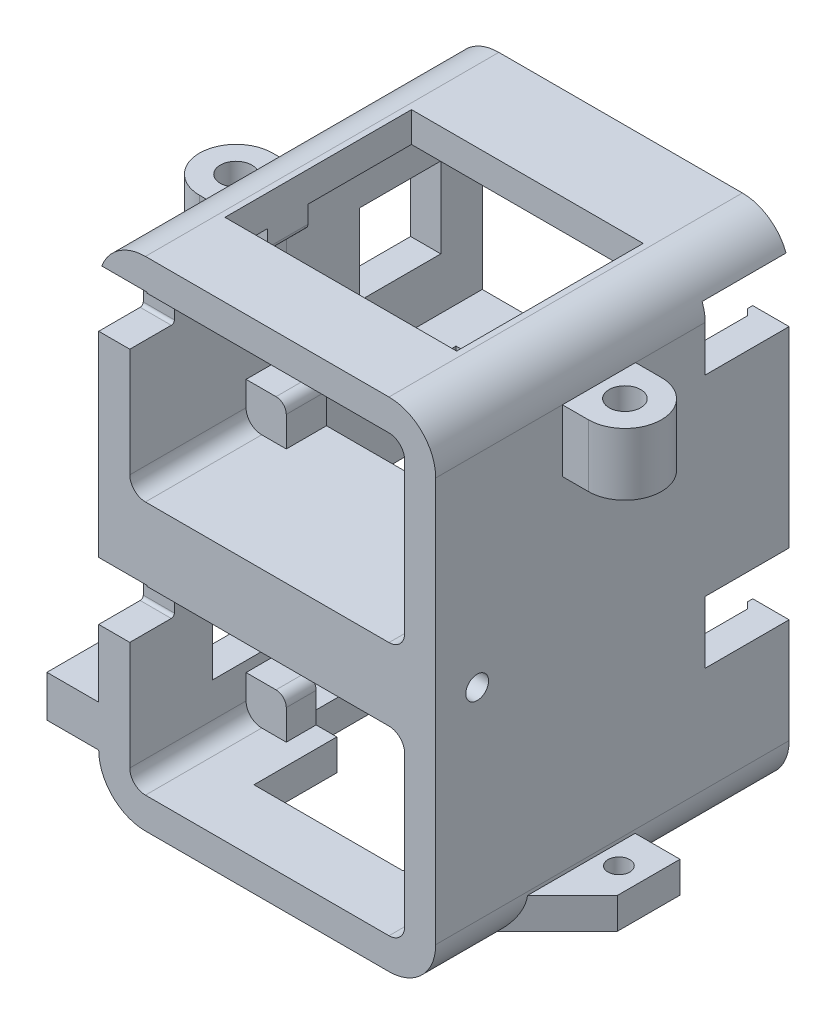
SolidWorks part; units mm, degrees
ref_plane "前视基准面" through (0, 0, 0) normal (0, 0, 1) x (1, 0, 0)
ref_plane "上视基准面" through (0, 0, 0) normal (0, 1, 0) x (1, 0, 0)
ref_plane "右视基准面" through (0, 0, 0) normal (1, 0, 0) x (0, 0, -1)
other "Configuration Table"
sketch "草图2" plane through (0, 0, 0) normal (0, 0, 1) x (1, 0, 0)
  line L20 (13.26, -7.25) -> (13.26, 7.25)
  line L21 (11.75, 8.76) -> (-16.76, 8.76)
  line L22 (-16.76, 8.76) -> (-16.76, 3.34)
  line L23 (-16.76, 3.34) -> (-13.26, 3.34)
  line L24 (-13.26, 3.34) -> (-13.26, -7.25)
  line L25 (-11.75, -8.76) -> (-3.99, -8.76)
  line L26 (-3.99, -8.76) -> (-3.99, -7.76)
  line L27 (-3.99, -7.76) -> (3.99, -7.76)
  line L28 (3.99, -7.76) -> (3.99, -8.76)
  line L29 (3.99, -8.76) -> (11.75, -8.76)
  line L40 (13.26, -7.25) -> (13.26, 7.25)
  line L41 (11.75, 8.76) -> (-16.76, 8.76)
  line L42 (-16.76, 8.76) -> (-16.76, 3.34)
  line L43 (-16.76, 3.34) -> (-13.26, 3.34)
  line L44 (-13.26, 3.34) -> (-13.26, -7.25)
  line L45 (-11.75, -8.76) -> (-3.99, -8.76)
  line L49 (3.99, -8.76) -> (11.75, -8.76)
  line L50 (-3.99, 15.74) -> (3.99, 15.74)
  line L51 (-3.99, -8.76) -> (3.99, -8.76)
  line L52 (-3.99, 12.74) -> (3.99, 12.74)
  line L53 (3.99, 12.74) -> (11.75, 12.74)
  line L54 (16.26, 17.25) -> (16.26, 31.75)
  line L55 (11.75, 36.26) -> (-19.76, 36.26)
  line L56 (-19.76, 36.26) -> (-19.76, 24.84)
  line L57 (-19.76, 24.84) -> (-16.26, 24.84)
  line L58 (-16.26, 24.84) -> (-16.26, 17.25)
  line L59 (-11.75, 12.74) -> (-3.99, 12.74)
  line L70 (13.26, 17.25) -> (13.26, 31.75)
  line L71 (11.75, 33.26) -> (-16.76, 33.26)
  line L72 (-16.76, 33.26) -> (-16.76, 27.84)
  line L73 (-16.76, 27.84) -> (-13.26, 27.84)
  line L74 (-13.26, 27.84) -> (-13.26, 17.25)
  line L75 (-11.75, 15.74) -> (-3.99, 15.74)
  line L76 (-3.99, 15.74) -> (-3.99, 16.74)
  line L77 (-3.99, 16.74) -> (3.99, 16.74)
  line L78 (3.99, 16.74) -> (3.99, 15.74)
  line L79 (3.99, 15.74) -> (11.75, 15.74)
  line L80 (13.26, 17.25) -> (13.26, 31.75)
  line L81 (11.75, 33.26) -> (-16.76, 33.26)
  line L82 (-16.76, 33.26) -> (-16.76, 27.84)
  line L83 (-16.76, 27.84) -> (-13.26, 27.84)
  line L84 (-13.26, 27.84) -> (-13.26, 17.25)
  line L85 (-11.75, 15.74) -> (-3.99, 15.74)
  line L89 (3.99, 15.74) -> (11.75, 15.74)
  line L90 (16.26, -7.25) -> (16.26, 7.25)
  line L91 (11.75, 11.76) -> (-19.76, 11.76)
  line L92 (-19.76, 11.76) -> (-19.76, 0.34)
  line L93 (-19.76, 0.34) -> (-16.26, 0.34)
  line L94 (-16.26, 0.34) -> (-16.26, -7.25)
  line L95 (-11.75, -11.76) -> (-3.99, -11.76)
  line L96 (-3.99, -11.76) -> (3.99, -11.76)
  line L97 (3.99, -11.76) -> (11.75, -11.76)
  line L98 (-16.26, 0.34) -> (-16.26, 3.34)
  line L99 (-16.26, 17.25) -> (-16.26, 11.76)
  line L100 (16.26, 17.25) -> (16.26, 7.25)
  line L101 (-16.76, 33.26) -> (-19.76, 33.26)
  line L102 (-16.76, 27.84) -> (-19.76, 27.84)
  line L103 (-16.76, 8.76) -> (-19.76, 8.76)
  line L104 (-16.26, 24.84) -> (-16.26, 27.84)
  line L105 (-16.26, 36.26) -> (-16.26, 33.26)
  line L106 (-16.26, 11.76) -> (-16.26, 8.76)
  line L107 (-16.26, 33.26) -> (-16.26, 27.84)
  line L108 (-16.26, 8.76) -> (-16.26, 3.34)
  line L109 (-13.26, 27.84) -> (-13.26, 33.26)
  line L110 (-13.26, 3.34) -> (-13.26, 8.76)
  arc A1 (-11.75, 11.76) -> (-16.26, 7.25) centre (-11.75, 7.25) ccw
  arc A2 (-11.75, 8.76) -> (-13.26, 7.25) centre (-11.75, 7.25) ccw
  arc A3 (-11.75, 8.76) -> (-13.26, 7.25) centre (-11.75, 7.25) ccw
  arc A6 (13.26, 7.25) -> (11.75, 8.76) centre (11.75, 7.25) ccw
  arc A7 (-13.26, -7.25) -> (-11.75, -8.76) centre (-11.75, -7.25) ccw
  arc A8 (11.75, -8.76) -> (13.26, -7.25) centre (11.75, -7.25) ccw
  arc A12 (13.26, 7.25) -> (11.75, 8.76) centre (11.75, 7.25) ccw
  arc A13 (-13.26, -7.25) -> (-11.75, -8.76) centre (-11.75, -7.25) ccw
  arc A14 (11.75, -8.76) -> (13.26, -7.25) centre (11.75, -7.25) ccw
  arc A15 (11.75, 12.74) -> (16.26, 17.25) centre (11.75, 17.25) ccw
  arc A16 (16.26, 31.75) -> (11.75, 36.26) centre (11.75, 31.75) ccw
  arc A17 (-16.26, 17.25) -> (-11.75, 12.74) centre (-11.75, 17.25) ccw
  arc A21 (13.26, 31.75) -> (11.75, 33.26) centre (11.75, 31.75) ccw
  arc A22 (-13.26, 17.25) -> (-11.75, 15.74) centre (-11.75, 17.25) ccw
  arc A23 (11.75, 15.74) -> (13.26, 17.25) centre (11.75, 17.25) ccw
  arc A24 (13.26, 31.75) -> (11.75, 33.26) centre (11.75, 31.75) ccw
  arc A25 (-13.26, 17.25) -> (-11.75, 15.74) centre (-11.75, 17.25) ccw
  arc A26 (11.75, 15.74) -> (13.26, 17.25) centre (11.75, 17.25) ccw
  arc A27 (16.26, 7.25) -> (11.75, 11.76) centre (11.75, 7.25) ccw
  arc A28 (-16.26, -7.25) -> (-11.75, -11.76) centre (-11.75, -7.25) ccw
  arc A29 (11.75, -11.76) -> (16.26, -7.25) centre (11.75, -7.25) ccw
  arc A31 (-11.75, 36.26) -> (-16.26, 31.75) centre (-11.75, 31.75) ccw
  arc A32 (-11.75, 33.26) -> (-13.26, 31.75) centre (-11.75, 31.75) ccw
  arc A33 (-11.75, 33.26) -> (-13.26, 31.75) centre (-11.75, 31.75) ccw
  dimension "D4" = 3
  dimension "D6" = 3
  dimension "D7" = 0.01
  dimension "D8" = 3
extrude "凸台-拉伸2" add sketch "草图2" against normal up to surface (11.22 mm away)
sketch "草图3" plane through (0, 0, -11.22) normal (0, 0, -1) x (-1, 0, 0)
  line L0 (11.75, -8.76) -> (-11.75, -8.76) construction
  line L2 (-11.75, 8.76) -> (11.75, 8.76) construction
  line L3 (11.75, -8.76) -> (-11.75, -8.76)
  line L4 (16.26, -7.25) -> (16.26, 31.75)
  line L5 (11.75, 36.26) -> (-11.75, 36.26)
  line L6 (-16.26, 31.75) -> (-16.26, -7.25)
  line L7 (-11.75, -11.76) -> (11.75, -11.76)
  line L12 (16.26, -7.25) -> (16.26, 31.75)
  line L13 (11.75, 36.26) -> (-11.75, 36.26)
  line L14 (-16.26, 31.75) -> (-16.26, -7.25)
  line L16 (-11.75, -11.76) -> (11.75, -11.76)
  line L20 (-13.26, -7.25) -> (-13.26, 7.25)
  line L21 (-11.75, 33.26) -> (11.75, 33.26) construction
  line L22 (-13.26, 17.25) -> (-13.26, 31.75) construction
  line L23 (-9.38, -8.74) -> (-9.38, -5.87)
  line L24 (-10.37, -4.88) -> (-13.24, -4.88)
  line L25 (-13.24, -4.88) -> (-13.24, -7.25)
  line L26 (-11.75, -8.74) -> (-9.38, -8.74)
  line L27 (-9.38, -8.74) -> (-9.38, -5.87)
  line L28 (-10.37, -4.88) -> (-13.24, -4.88)
  line L32 (11.75, 15.74) -> (-11.75, 15.74) construction
  line L33 (-11.75, 33.26) -> (11.75, 33.26)
  line L34 (-13.26, 17.25) -> (-13.26, 31.75)
  line L36 (11.75, 15.74) -> (-11.75, 15.74)
  line L38 (13.26, 7.25) -> (13.26, -7.25) construction
  line L39 (13.24, -4.88) -> (10.37, -4.88)
  line L40 (9.38, -5.87) -> (9.38, -8.74)
  line L41 (9.38, -8.74) -> (11.75, -8.74)
  line L42 (13.24, -7.25) -> (13.24, -4.88)
  line L43 (13.24, -4.88) -> (10.37, -4.88)
  line L44 (9.38, -5.87) -> (9.38, -8.74)
  line L47 (13.26, 7.25) -> (13.26, -7.25)
  line L48 (-11.75, 8.76) -> (11.75, 8.76) construction
  line L49 (-9.38, 15.75) -> (-9.38, 18.63)
  line L50 (-10.37, 19.62) -> (-13.25, 19.62)
  line L51 (-13.24, 6.68) -> (-11.67, 6.68)
  line L52 (-11.18, 7.17) -> (-11.18, 8.74)
  line L53 (-11.18, 8.74) -> (-11.75, 8.74)
  line L54 (-13.24, 7.25) -> (-13.24, 6.68)
  line L55 (-13.24, 6.68) -> (-11.67, 6.68)
  line L56 (-11.18, 7.17) -> (-11.18, 8.74)
  line L59 (-13.24, 6.68) -> (-13.26, 6.68)
  line L60 (-13.26, -7.25) -> (-13.26, 7.25) construction
  line L61 (-9.38, 15.74) -> (-9.38, 18.63)
  line L62 (-10.37, 19.62) -> (-13.26, 19.62)
  line L63 (11.18, 8.74) -> (11.18, 7.17)
  line L64 (11.67, 6.68) -> (13.24, 6.68)
  line L65 (13.24, 6.68) -> (13.24, 7.25)
  line L66 (11.75, 8.74) -> (11.18, 8.74)
  line L67 (11.18, 8.76) -> (11.18, 7.17)
  line L68 (11.67, 6.68) -> (13.26, 6.68)
  line L71 (-11.75, 8.76) -> (11.75, 8.76)
  line L73 (-13.25, 31.18) -> (-11.67, 31.18)
  line L74 (-11.18, 31.67) -> (-11.18, 33.25)
  line L75 (-13.25, 31.18) -> (-11.67, 31.18)
  line L76 (-11.18, 31.67) -> (-11.18, 33.25)
  line L79 (11.67, 31.18) -> (13.25, 31.18)
  line L80 (11.18, 33.25) -> (11.18, 31.67)
  line L81 (11.67, 31.18) -> (13.26, 31.18)
  line L82 (11.18, 33.25) -> (11.18, 31.67)
  line L83 (-13.25, 31.18) -> (-13.26, 31.18)
  line L84 (-11.18, 33.25) -> (-11.18, 33.26)
  line L85 (9.38, 18.63) -> (9.38, 15.75)
  line L86 (13.25, 19.62) -> (10.37, 19.62)
  line L87 (9.38, 18.63) -> (9.38, 15.74)
  line L88 (13.26, 19.62) -> (10.37, 19.62)
  line L89 (11.18, 33.25) -> (11.18, 33.26)
  line L90 (-11.18, 8.74) -> (-11.18, 8.76)
  line L91 (13.26, 31.75) -> (13.26, 17.25) construction
  line L92 (13.26, 31.75) -> (13.26, 17.25)
  line L93 (-13.24, -4.88) -> (-13.26, -4.88)
  line L94 (-9.38, -8.74) -> (-9.38, -8.76)
  line L95 (9.38, -8.74) -> (9.38, -8.76)
  line L96 (13.24, -4.88) -> (13.26, -4.88)
  arc A0 (-13.26, -7.25) -> (-11.75, -8.76) centre (-11.75, -7.25) ccw construction
  arc A1 (11.75, -8.76) -> (13.26, -7.25) centre (11.75, -7.25) ccw construction
  arc A2 (-11.75, 8.76) -> (-13.26, 7.25) centre (-11.75, 7.25) ccw construction
  arc A3 (11.75, -11.76) -> (16.26, -7.25) centre (11.75, -7.25) ccw
  arc A4 (-11.75, 36.26) -> (-16.26, 31.75) centre (-11.75, 31.75) ccw
  arc A5 (-16.26, -7.25) -> (-11.75, -11.76) centre (-11.75, -7.25) ccw
  arc A6 (11.75, -11.76) -> (16.26, -7.25) centre (11.75, -7.25) ccw
  arc A9 (-11.75, 36.26) -> (-16.26, 31.75) centre (-11.75, 31.75) ccw
  arc A10 (-9.38, -5.87) -> (-10.37, -4.88) centre (-10.37, -5.87) ccw
  arc A11 (-13.24, -7.25) -> (-11.75, -8.74) centre (-11.75, -7.25) ccw
  arc A12 (-9.38, -5.87) -> (-10.37, -4.88) centre (-10.37, -5.87) ccw
  arc A14 (-16.26, -7.25) -> (-11.75, -11.76) centre (-11.75, -7.25) ccw
  arc A15 (-13.26, -7.25) -> (-11.75, -8.76) centre (-11.75, -7.25) ccw
  arc A16 (11.75, -8.76) -> (13.26, -7.25) centre (11.75, -7.25) ccw
  arc A17 (-11.75, 8.76) -> (-13.26, 7.25) centre (-11.75, 7.25) ccw
  arc A18 (10.37, -4.88) -> (9.38, -5.87) centre (10.37, -5.87) ccw
  arc A19 (11.75, -8.74) -> (13.24, -7.25) centre (11.75, -7.25) ccw
  arc A20 (10.37, -4.88) -> (9.38, -5.87) centre (10.37, -5.87) ccw
  arc A22 (-11.75, 33.26) -> (-13.26, 31.75) centre (-11.75, 31.75) ccw construction
  arc A23 (11.75, 15.74) -> (13.26, 17.25) centre (11.75, 17.25) ccw construction
  arc A24 (-11.67, 6.68) -> (-11.18, 7.17) centre (-11.67, 7.17) ccw
  arc A25 (-11.75, 8.74) -> (-13.24, 7.25) centre (-11.75, 7.25) ccw
  arc A26 (-11.67, 6.68) -> (-11.18, 7.17) centre (-11.67, 7.17) ccw
  arc A28 (-13.26, 17.25) -> (-11.75, 15.74) centre (-11.75, 17.25) ccw construction
  arc A29 (-11.75, 33.26) -> (-13.26, 31.75) centre (-11.75, 31.75) ccw
  arc A30 (11.18, 7.17) -> (11.67, 6.68) centre (11.67, 7.17) ccw
  arc A31 (13.24, 7.25) -> (11.75, 8.74) centre (11.75, 7.25) ccw
  arc A32 (11.18, 7.17) -> (11.67, 6.68) centre (11.67, 7.17) ccw
  arc A34 (11.75, 15.74) -> (13.26, 17.25) centre (11.75, 17.25) ccw
  arc A35 (-13.26, 17.25) -> (-11.75, 15.74) centre (-11.75, 17.25) ccw
  arc A36 (13.26, 7.25) -> (11.75, 8.76) centre (11.75, 7.25) ccw construction
  arc A37 (13.26, 7.25) -> (11.75, 8.76) centre (11.75, 7.25) ccw
  arc A38 (-9.38, 18.63) -> (-10.37, 19.62) centre (-10.37, 18.63) ccw
  arc A39 (-9.38, 18.63) -> (-10.37, 19.62) centre (-10.37, 18.63) ccw
  arc A41 (-11.67, 31.18) -> (-11.18, 31.67) centre (-11.67, 31.67) ccw
  arc A42 (-11.67, 31.18) -> (-11.18, 31.67) centre (-11.67, 31.67) ccw
  arc A44 (11.18, 31.67) -> (11.67, 31.18) centre (11.67, 31.67) ccw
  arc A45 (11.18, 31.67) -> (11.67, 31.18) centre (11.67, 31.67) ccw
  arc A46 (13.26, 31.75) -> (11.75, 33.26) centre (11.75, 31.75) ccw construction
  arc A47 (10.37, 19.62) -> (9.38, 18.63) centre (10.37, 18.63) ccw
  arc A48 (10.37, 19.62) -> (9.38, 18.63) centre (10.37, 18.63) ccw
  arc A49 (13.26, 31.75) -> (11.75, 33.26) centre (11.75, 31.75) ccw
  arc A52 (16.26, 31.75) -> (11.75, 36.26) centre (11.75, 31.75) ccw
  arc A53 (16.26, 31.75) -> (11.75, 36.26) centre (11.75, 31.75) ccw
  dimension "D7" = 0.01
  dimension "D9" = 0.01
extrude "凸台-拉伸3" add sketch "草图3" along normal up to surface (3.88 mm away)
sketch "草图4" plane through (-16.26, 0, 0) normal (-1, 0, 0) x (0, 0, 1)
  line L8 (0.1, 8.85) -> (-4, 8.85)
  line L9 (-4.3, 8.55) -> (-4.3, 3.55)
  line L10 (-4, 3.25) -> (0.1, 3.25)
  line L11 (0.1, 3.25) -> (0.1, 8.85)
  line L12 (0.1, 8.85) -> (-4, 8.85)
  line L13 (-4.3, 8.55) -> (-4.3, 3.55)
  line L14 (-4, 3.25) -> (0.1, 3.25)
  line L15 (0.1, 3.25) -> (0.1, 8.85)
  line L20 (0.1, 33.35) -> (-4, 33.35)
  line L21 (-4.3, 33.05) -> (-4.3, 28.05)
  line L22 (-4, 27.75) -> (0.1, 27.75)
  line L23 (0.1, 27.75) -> (0.1, 33.35)
  line L24 (0.1, 33.35) -> (-4, 33.35)
  line L25 (-4.3, 33.05) -> (-4.3, 28.05)
  line L26 (-4, 27.75) -> (0.1, 27.75)
  line L27 (0.1, 27.75) -> (0.1, 33.35)
  arc A4 (-4, 8.85) -> (-4.3, 8.55) centre (-4, 8.55) ccw
  arc A5 (-4.3, 3.55) -> (-4, 3.25) centre (-4, 3.55) ccw
  arc A6 (-4, 8.85) -> (-4.3, 8.55) centre (-4, 8.55) ccw
  arc A7 (-4.3, 3.55) -> (-4, 3.25) centre (-4, 3.55) ccw
  arc A10 (-4, 33.35) -> (-4.3, 33.05) centre (-4, 33.05) ccw
  arc A11 (-4.3, 28.05) -> (-4, 27.75) centre (-4, 28.05) ccw
  arc A12 (-4, 33.35) -> (-4.3, 33.05) centre (-4, 33.05) ccw
  arc A13 (-4.3, 28.05) -> (-4, 27.75) centre (-4, 28.05) ccw
extrude "切除-拉伸1" cut sketch "草图4" against normal blind 4.65
ref_plane "基准面1" through (0, 31.75, 0) normal (0, 1, 0) x (1, 0, 0)
sketch "草图8" plane through (0, 31.75, 0) normal (0, 1, 0) x (1, 0, 0)
  line L0 (18.76, 12.23) -> (15.235, 12.23)
  line L1 (15.235, 12.23) -> (15.235, 15.755)
  line L2 (16.26, 15.1) -> (16.26, 0) construction
  line L3 (-12.113, 15.755) -> (15.235, 15.755) construction
  line L4 (9.73, 15.91) -> (-9.73, 15.91) construction
  line L5 (-9.73, 15.6) -> (9.73, 15.6) construction
  line L9 (18.76, 19.28) -> (15.235, 19.28)
  line L10 (15.235, 15.755) -> (15.235, 19.28)
  circle A2 centre (18.76, 15.755) radius 1.525
  circle A3 centre (18.76, 15.755) radius 3.525
  dimension "D1" = 3.05
  dimension "D3" = 2.5
  dimension "D2" = 2
extrude "凸台-拉伸5" add sketch "草图8" against normal blind 6 contours A3 A2 | A3 L9 L10 | A3 L1 L0
mirror "镜向1" about plane through (0, 0, 0) normal (1, 0, 0) of "凸台-拉伸5"
sketch "草图9" plane through (0, 0, -15.1) normal (0, 0, -1) x (-1, 0, 0)
  line L0 (-11.18, 33.26) -> (11.18, 33.26) construction
  line L1 (-11.18, 33.26) -> (11.18, 33.26)
  line L2 (-11.18, 33.26) -> (-11.18, 36.26)
  line L3 (-11.18, 36.26) -> (11.18, 36.26)
  line L4 (11.18, 33.26) -> (11.18, 36.26)
  line L5 (11.75, 36.26) -> (-11.75, 36.26) construction
  line L6 (-11.18, 31.67) -> (-11.18, 33.26) construction
  line L7 (11.18, 33.26) -> (11.18, 31.67) construction
extrude "切除-拉伸3" cut sketch "草图9" against normal blind 8
sketch "草图10" plane through (0, 0, -15.1) normal (0, 0, -1) x (-1, 0, 0)
  line L0 (-11.75, -11.76) -> (11.75, -11.76) construction
  line L1 (-10.73, -11.76) -> (10.73, -11.76)
  line L2 (-10.73, -11.76) -> (-10.73, -4.88)
  line L3 (-10.73, -4.88) -> (10.73, -4.88)
  line L4 (10.73, -11.76) -> (10.73, -4.88)
  line L5 (13.26, -4.88) -> (10.37, -4.88) construction
  line L6 (-9.73, 21.7989) -> (-9.73, 20.8989) construction
  line L7 (9.73, 69.5489) -> (9.73, -48.1511) construction
  dimension "D1" = 1
  dimension "D2" = 1
extrude "切除-拉伸4" cut sketch "草图10" against normal blind 1
sketch "草图12" plane through (-16.26, 0, 0) normal (-1, 0, 0) x (0, 0, 1)
  line L0 (0, 8.85) -> (0, 27.75) construction
  line L1 (-11.22, 8.76) -> (-4.2142, 8.76) construction
  line L2 (-11.22, 15.74) -> (0, 15.74) construction
  line L3 (-11.22, 8.76) -> (-4.2142, 8.76)
  line L4 (-11.22, 15.74) -> (0, 15.74)
  line L5 (-8.8508, 12.25) -> (0.722, 12.25) construction
  circle A0 centre (-4, 12.25) radius 1.1
  dimension "D1" = 2.2
  dimension "D2" = 4
extrude "切除-拉伸5" cut sketch "草图12" against normal blind 8 contours A0 L5 | L5 A0
mirror "镜向2" about plane through (0, 0, 0) normal (1, 0, 0) of "切除-拉伸5"
sketch "草图14" plane through (0, 0, -15.1) normal (0, 0, -1) x (-1, 0, 0)
  line L0 (-16.26, 19.53) -> (16.26, 19.53)
  line L2 (-16.26, 8.85) -> (16.26, 8.85)
  line L3 (-10.37, 19.63) -> (-13.25, 19.63) construction
  line L6 (9.88, -48.3011) -> (9.88, 69.6193)
  line L7 (-9.88, -48.3011) -> (9.88, -48.3011)
  line L8 (-9.88, 69.6193) -> (-9.88, -48.3011)
  line L9 (9.88, -48.3011) -> (9.88, 69.6193)
  line L10 (-9.88, -48.3011) -> (9.88, -48.3011)
  line L11 (-9.88, 69.6193) -> (-9.88, -48.3011)
  line L13 (-11.17, 8.75) -> (11.17, 8.75) construction
  line L19 (16.26, 3.25) -> (13.26, 3.25)
  line L20 (16.26, -7.25) -> (16.26, 3.25)
  line L21 (-11.75, -11.76) -> (11.75, -11.76)
  line L22 (-16.26, 31.75) -> (-16.26, -7.25)
  line L23 (11.75, 36.26) -> (-11.75, 36.26)
  line L24 (11.61, 33.35) -> (15.9666, 33.35)
  line L26 (-11.75, 33.26) -> (11.61, 33.26)
  line L27 (-13.26, 17.25) -> (-13.26, 31.75)
  line L28 (11.75, 15.74) -> (-11.75, 15.74)
  line L29 (13.26, 27.75) -> (13.26, 17.25)
  line L30 (16.26, 27.75) -> (13.26, 27.75)
  line L31 (16.26, 8.85) -> (16.26, 27.75)
  line L32 (11.61, 8.85) -> (16.26, 8.85)
  line L34 (-11.75, 8.76) -> (11.61, 8.76)
  line L35 (-13.26, -7.25) -> (-13.26, 7.25)
  line L36 (11.75, -8.76) -> (-11.75, -8.76)
  line L37 (13.26, 3.25) -> (13.26, -7.25)
  line L39 (16.26, -7.25) -> (16.26, 8.85)
  line L40 (-11.75, -11.76) -> (11.75, -11.76)
  line L41 (-16.26, 31.75) -> (-16.26, -7.25)
  line L42 (11.75, 36.26) -> (-11.75, 36.26)
  line L50 (16.26, 8.85) -> (16.26, 31.75)
  line L66 (11.61, 33.26) -> (11.61, 33.35)
  line L67 (11.61, 8.76) -> (11.61, 8.85)
  arc A2 (9.88, 69.6193) -> (-9.88, 69.6193) centre (0, 57.7742) ccw
  arc A3 (9.88, 69.6193) -> (-9.88, 69.6193) centre (0, 57.7742) ccw
  arc A10 (11.75, -11.76) -> (16.26, -7.25) centre (11.75, -7.25) ccw
  arc A11 (-16.26, -7.25) -> (-11.75, -11.76) centre (-11.75, -7.25) ccw
  arc A12 (-11.75, 36.26) -> (-16.26, 31.75) centre (-11.75, 31.75) ccw
  arc A13 (15.9666, 33.35) -> (11.75, 36.26) centre (11.75, 31.75) ccw
  arc A14 (-11.75, 33.26) -> (-13.26, 31.75) centre (-11.75, 31.75) ccw
  arc A15 (-13.26, 17.25) -> (-11.75, 15.74) centre (-11.75, 17.25) ccw
  arc A16 (11.75, 15.74) -> (13.26, 17.25) centre (11.75, 17.25) ccw
  arc A17 (-11.75, 8.76) -> (-13.26, 7.25) centre (-11.75, 7.25) ccw
  arc A18 (-13.26, -7.25) -> (-11.75, -8.76) centre (-11.75, -7.25) ccw
  arc A19 (11.75, -8.76) -> (13.26, -7.25) centre (11.75, -7.25) ccw
  arc A20 (11.75, -11.76) -> (16.26, -7.25) centre (11.75, -7.25) ccw
  arc A21 (-16.26, -7.25) -> (-11.75, -11.76) centre (-11.75, -7.25) ccw
  arc A22 (-11.75, 36.26) -> (-16.26, 31.75) centre (-11.75, 31.75) ccw
  arc A23 (16.26, 31.75) -> (11.75, 36.26) centre (11.75, 31.75) ccw
  dimension "D3" = 0.1
  dimension "D4" = 0.1
  dimension "D2" = 0.15
extrude "凸台-拉伸7" add sketch "草图14" along normal blind 3
sketch "草图15" plane through (0, 0, -15.1) normal (0, 0, -1) x (-1, 0, 0)
  line L0 (-16.26, 25.75) -> (-16.26, 19.53) construction
  line L7 (-16.26, 19.53) -> (-16.26, 8.85) construction
  line L8 (-16.26, 8.85) -> (-16.26, -7.25) construction
  line L10 (-10.73, -11.76) -> (10.73, -11.76) construction
  line L22 (16.26, -7.25) -> (16.26, 8.85) construction
  line L23 (16.26, 8.85) -> (16.26, 19.53) construction
  line L32 (16.26, 19.53) -> (16.26, 25.75) construction
  line L37 (11.18, 36.26) -> (-11.18, 36.26) construction
  line L38 (-16.26, 31.75) -> (-16.26, 19.53)
  line L39 (-16.26, 19.53) -> (-16.26, 8.85)
  line L42 (-16.26, 8.85) -> (-16.26, -7.25)
  line L43 (-11.75, -11.76) -> (11.75, -11.76)
  line L44 (16.26, -7.25) -> (16.26, 8.85)
  line L45 (16.26, 8.85) -> (16.26, 19.53)
  line L46 (16.26, 19.53) -> (16.26, 31.75)
  line L47 (11.75, 36.26) -> (-11.75, 36.26)
  line L48 (-11.17, 33.25) -> (11.17, 33.25) construction
  line L49 (-13.35, 33.35) -> (13.35, 33.35)
  line L54 (-13.35, 33.35) -> (-13.35, -8.85)
  line L55 (-13.35, -8.85) -> (13.35, -8.85)
  line L56 (13.35, 33.35) -> (13.35, -8.85)
  line L58 (13.25, 6.67) -> (13.25, -4.87) construction
  line L59 (9.37, -8.75) -> (-9.37, -8.75) construction
  line L60 (-13.25, -4.87) -> (-13.25, 6.67) construction
  arc A8 (-16.26, -7.25) -> (-11.75, -11.76) centre (-11.75, -7.25) ccw construction
  arc A9 (11.75, -11.76) -> (16.26, -7.25) centre (11.75, -7.25) ccw construction
  arc A10 (16.26, 31.75) -> (11.75, 36.26) centre (11.75, 31.75) ccw construction
  arc A11 (-11.75, 36.26) -> (-16.26, 31.75) centre (-11.75, 31.75) ccw construction
  arc A12 (-16.26, -7.25) -> (-11.75, -11.76) centre (-11.75, -7.25) ccw
  arc A13 (11.75, -11.76) -> (16.26, -7.25) centre (11.75, -7.25) ccw
  arc A14 (16.26, 31.75) -> (11.75, 36.26) centre (11.75, 31.75) ccw
  arc A15 (-11.75, 36.26) -> (-16.26, 31.75) centre (-11.75, 31.75) ccw
  dimension "D2" = 0.1
  dimension "D1" = 0.1
  dimension "D3" = 0.1
  dimension "D4" = 0.1
extrude "凸台-上半部分" add sketch "草图15" along normal blind 19
sketch "草图16" plane through (0, 0, -18.1) normal (0, 0, -1) x (-1, 0, 0)
  line L1 (-13.35, 8.85) -> (13.35, 8.85)
  line L2 (-13.35, 8.85) -> (-13.35, 15.65)
  line L3 (-13.35, 15.65) -> (13.35, 15.65)
  line L4 (13.35, 8.85) -> (13.35, 15.65)
  line L12 (-13.35, 33.35) -> (-13.35, -8.85) construction
  line L13 (13.35, 33.35) -> (13.35, -8.85) construction
  line L15 (-4, 15.75) -> (-11.75, 15.75) construction
  line L16 (-11.17, 8.75) -> (11.17, 8.75) construction
  dimension "D2" = 0.1
  dimension "D1" = 0.1
extrude "凸台-拉伸9" add sketch "草图16" along normal up to surface (16 mm away) up to face at (0, 12.25, -34.1)
sketch "草图11" plane through (0, -13.58, 0) normal (0, 1, 0) x (1, 0, 0)
  line L2 (11.75, 34.1) -> (11.75, 0)
  line L3 (11.75, 34.1) -> (11.75, 0) construction
  line L7 (15.88, 21.655) -> (15.88, 16.405)
  line L8 (15.88, 16.405) -> (17.4201, 16.405)
  line L9 (17.4201, 15.105) -> (15.88, 15.105)
  line L10 (15.88, 15.105) -> (15.88, 9.855)
  line L11 (15.88, 9.855) -> (20.58, 9.855)
  line L12 (20.58, 9.855) -> (20.58, 21.655)
  line L13 (20.58, 21.655) -> (15.88, 21.655)
  line L19 (20.58, 13.9124) -> (20.58, 18.755)
  line L21 (11.75, 18.755) -> (20.58, 18.755)
  line L22 (20.58, 13.9124) -> (11.75, 5.0824)
  circle A0 centre (18.18, 15.755) radius 1.1
  arc A1 (17.4201, 15.105) -> (17.4201, 16.405) centre (18.18, 15.755) ccw
  line M15 (15.88, 21.655) -> (15.88, 16.405)
  line M16 (15.88, 16.405) -> (17.4201, 16.405)
  line M18 (17.4201, 15.105) -> (15.88, 15.105)
  line M19 (15.88, 15.105) -> (15.88, 9.855)
  line M20 (15.88, 9.855) -> (20.58, 9.855)
  line M21 (20.58, 9.855) -> (20.58, 21.655)
  dimension "D6" = 2.2
  dimension "D2" = 3
  dimension "D5" = 45
  dimension "D7" = 3
  dimension "D1" = 0
extrude "凸台-舵机固定孔位" [suppressed] add sketch "草图11" along normal blind 4 contours A0 L21 L2 L22 M16 M15 M20 M19 M18 | A0 L22 L21 M18 M19 M20 M21 M15 M16
sketch "草图17" plane through (0, 8.85, 0) normal (0, -1, 0) x (1, 0, 0)
  line L2 (11.75, -34.1) -> (-11.75, -34.1) construction
  line L3 (-9.88, -18.1) -> (9.88, -18.1)
  line L5 (-9.88, -18.1) -> (9.88, -18.1)
  line L6 (-9.88, -18.1) -> (-9.88, -28.1)
  line L7 (-9.88, -28.1) -> (9.88, -28.1)
  line L8 (9.88, -18.1) -> (9.88, -28.1)
  line L9 (9.88, -18.1) -> (9.88, -15.1) construction
  line L10 (9.88, -18.1) -> (-9.88, -18.1) construction
  line L12 (-9.88, -18.1) -> (-9.88, -15.1) construction
  dimension "D1" = 6
extrude "切除-拉伸8" cut sketch "草图17" against normal up to next contours L8 L3 L6 L7
sketch "草图18" plane through (13.35, 0, 0) normal (-1, 0, 0) x (0, 0, 1)
  line L0 (0, -7.25) -> (0, 31.75) construction
  line L1 (-34.1, 2.85) -> (-26, 2.85)
  line L2 (-34.1, 2.85) -> (-34.1, 8.85)
  line L3 (-34.1, 8.85) -> (-26, 8.85)
  line L4 (-26, 2.85) -> (-26, 8.85)
  line L5 (-34.1, 27.35) -> (-26, 27.35)
  line L6 (-34.1, 27.35) -> (-34.1, 33.35)
  line L7 (-34.1, 33.35) -> (-26, 33.35)
  line L8 (-26, 27.35) -> (-26, 33.35)
  line L9 (-34.1, -7.25) -> (-34.1, 31.75) construction
  line L10 (-34.1, 8.85) -> (-34.1, -8.85) construction
  line L11 (-34.1, 8.85) -> (-15.1, 8.85) construction
  dimension "D2" = 6
  dimension "D3" = 6
  dimension "D5" = 26
extrude "切除-拉伸9" cut sketch "草图18" against normal up to next
sketch "草图19" plane through (0, -11.76, 0) normal (0, -1, 0) x (1, 0, 0)
  line L1 (-10.73, -14.1) -> (10.73, -14.1)
  line L2 (-10.73, -14.1) -> (-10.73, -15.1)
  line L3 (-10.73, -15.1) -> (10.73, -15.1)
  line L4 (10.73, -14.1) -> (10.73, -15.1)
  line L5 (-10.73, -15.1) -> (10.73, -15.1)
  line L6 (-10.73, -15.1) -> (-10.73, -25.1)
  line L7 (-10.73, -25.1) -> (10.73, -25.1)
  line L8 (10.73, -15.1) -> (10.73, -25.1)
  dimension "D1" = 10
extrude "切除-拉伸10" cut sketch "草图19" against normal up to next
sketch "草图24" plane through (0, -11.76, 0) normal (0, -1, 0) x (1, 0, 0)
  line L0 (9.38, -14.1) -> (-9.38, -14.1) construction
  line L1 (9.38, -14.1) -> (-9.38, -14.1)
  line L3 (-7, -6.1) -> (7, -6.1)
  line L4 (-7, -6.1) -> (-7, -14.1)
  line L5 (-7, -14.1) -> (7, -14.1)
  line L6 (7, -6.1) -> (7, -14.1)
  line L7 (-7, -6.1) -> (7, -14.1) construction
  line L8 (-7, -14.1) -> (7, -6.1) construction
  point P2 (0, -10.1)
  dimension "D1" = 8
  dimension "D2" = 14
extrude "切除-拉伸14" cut sketch "草图24" against normal up to next contours L6 L3 L4 L1
sketch "草图20" plane through (0, 36.26, 0) normal (0, 1, 0) x (1, 0, 0)
  line L1 (-11.18, 15.1) -> (11.18, 15.1)
  line L2 (-11.18, 15.1) -> (-11.18, 25.1)
  line L3 (-11.18, 25.1) -> (11.18, 25.1)
  line L4 (11.18, 15.1) -> (11.18, 25.1)
  dimension "D1" = 10
extrude "切除-拉伸11" cut sketch "草图20" against normal up to next
sketch "草图21" plane through (13.35, 0, 0) normal (-1, 0, 0) x (0, 0, 1)
  line L0 (-34.1, 27.35) -> (-34.1, 15.65) construction
  line L5 (-34.1, 2.85) -> (-26, 2.85) construction
  line L6 (-34.1, 27.35) -> (-32.6, 27.35)
  line L7 (-34.1, 27.35) -> (-34.1, 22.35)
  line L8 (-34.1, 22.35) -> (-32.6, 22.35)
  line L9 (-32.6, 27.35) -> (-32.6, 22.35)
  line L10 (-34.1, 2.85) -> (-32.6, 2.85)
  line L11 (-34.1, 2.85) -> (-34.1, -2.15)
  line L12 (-34.1, -2.15) -> (-32.6, -2.15)
  line L13 (-32.6, 2.85) -> (-32.6, -2.15)
  dimension "D1" = 5
  dimension "D2" = 1.5
extrude "凸台-拉伸10" add sketch "草图21" along normal blind 0.6
chamfer "倒角1" distance 1 angle 45 2 edges at (12.75, 0.35, -32.6) (12.75, 24.85, -32.6)
sketch "草图22" plane through (-16.26, 0, 0) normal (-1, 0, 0) x (0, 0, 1)
  line L0 (-15.1, 6.68) -> (-15.1, -4.88) construction
  line L1 (-15.1, 6.68) -> (-15.1, -4.88)
  line L2 (-44.3237, 0.9) -> (-2.0599, 0.9) construction
  line L3 (-34.1, 15.65) -> (-18.1, 15.65) construction
  line L4 (-30.1, 5.68) -> (-8, 5.68)
  line L5 (-30.1, 5.68) -> (-30.1, -3.88)
  line L6 (-30.1, -3.88) -> (-8, -3.88)
  line L7 (-8, 5.68) -> (-8, -3.88)
  line L8 (-30.1, 5.68) -> (-8, -3.88) construction
  line L9 (-30.1, -3.88) -> (-8, 5.68) construction
  line L10 (0, -7.25) -> (0, 3.25) construction
  line L11 (-45.0764, 24.5) -> (-5.8743, 24.5) construction
  line L12 (-15.1, 31.18) -> (-15.1, 19.62) construction
  line L13 (-30.1, 28.38) -> (-22.2401, 28.38)
  line L14 (-30.1, 28.38) -> (-30.1, 20.62)
  line L15 (-30.1, 20.62) -> (-22.2401, 20.62)
  line L16 (-22.2401, 28.38) -> (-22.2401, 20.62)
  line L17 (-34.1, 33.35) -> (-15.1, 33.35) construction
  line L23 (-34.1, 15.65) -> (-18.1, 15.65)
  line L24 (-34.1, 33.35) -> (-34.1, 15.65)
  line L25 (-15.1, 33.35) -> (-34.1, 33.35)
  line L26 (-15.1, 18.68) -> (-15.1, 33.35)
  line L27 (-18.1, 18.68) -> (-15.1, 18.68)
  line L28 (-18.1, 15.65) -> (-18.1, 18.68)
  line L29 (-30.1, 28.38) -> (-22.2401, 20.62) construction
  line L30 (-30.1, 20.62) -> (-22.2401, 28.38) construction
  line L31 (-15.1, 31.18) -> (-15.1, 19.62)
  line L32 (-18.2401, 25.75) -> (-18.2401, 31.75) construction
  line L33 (-18.2401, 25.75) -> (-18.2401, 31.75)
  line L35 (-34.1, -7.25) -> (-34.1, 31.75) construction
  point P2 (-15.1, 0.9)
  point P5 (-19.05, 0.9)
  point P20 (-26.17, 24.5)
  dimension "D1" = 4
  dimension "D2" = 8
  dimension "D3" = 1
  dimension "D5" = 1
  dimension "D6" = 4
extrude "切除-拉伸12" cut sketch "草图22" against normal up to next contours L5 L6 L1 L4 | L7 L4 L1 L6 | L16 L13 L14 L15
sketch "草图23" plane through (0, -11.76, 0) normal (0, -1, 0) x (1, 0, 0)
  line L0 (10.73, -14.1) -> (7, -14.1) construction
  line L1 (-7.38, -6.1) -> (7.38, -6.1)
  line L2 (-7.38, -6.1) -> (-7.38, -14.1)
  line L3 (-7.38, -14.1) -> (7.38, -14.1)
  line L4 (7.38, -6.1) -> (7.38, -14.1)
  line L5 (-7.38, -6.1) -> (7.38, -14.1) construction
  line L6 (-7.38, -14.1) -> (7.38, -6.1) construction
  line L8 (9.38, -14.1) -> (9.38, -11.22)
  line L9 (7, -14.1) -> (9.38, -14.1)
  line L10 (-9.38, -11.22) -> (-9.38, -14.1)
  line L11 (-11.75, -11.22) -> (-9.38, -11.22)
  line L12 (-11.75, 0) -> (-11.75, -11.22)
  line L13 (11.75, 0) -> (-11.75, 0)
  line L14 (11.75, -11.22) -> (11.75, 0)
  line L15 (9.38, -11.22) -> (11.75, -11.22)
  line L16 (9.38, -14.1) -> (9.38, -11.22)
  line L17 (7, -14.1) -> (9.38, -14.1)
  line L18 (-9.38, -11.22) -> (-9.38, -14.1)
  line L19 (-11.75, -11.22) -> (-9.38, -11.22)
  line L20 (-11.75, 0) -> (-11.75, -11.22)
  line L21 (11.75, 0) -> (-11.75, 0)
  line L22 (11.75, -11.22) -> (11.75, 0)
  line L23 (9.38, -11.22) -> (11.75, -11.22)
  line L35 (7, -6.1) -> (7, -14.1)
  line L36 (7, -6.1) -> (7, -14.1)
  line L37 (-7, -6.1) -> (7, -6.1)
  line L38 (-7, -6.1) -> (7, -6.1)
  line L39 (-7, -14.1) -> (-7, -6.1)
  line L40 (-7, -14.1) -> (-7, -6.1)
  line L41 (-9.38, -14.1) -> (-7, -14.1)
  line L42 (-9.38, -14.1) -> (-7, -14.1)
  point P2 (0, -10.1)
  line M19 (-10.73, -14.1) -> (-7, -14.1)
  dimension "D2" = 2
  dimension "D3" = 8
  dimension "D1" = 0
extrude "切除-拉伸13" cut sketch "草图23" against normal up to next contours L4 L1 L2 M19
ref_plane "基准面2" through (0, -10.58, 0) normal (0, 1, 0) x (1, 0, 0)
sketch "草图25" plane through (0, -10.58, 0) normal (0, 1, 0) x (1, 0, 0)
  line L2 (14.58, 19.255) -> (14.58, 7.2053)
  line L3 (20.58, 9.855) -> (20.58, 21.655) construction
  line L4 (20.58, 13.2053) -> (14.58, 7.2053)
  line L6 (20.58, 13.2053) -> (20.58, 19.255)
  line L8 (14.58, 19.255) -> (20.58, 19.255)
  arc A0 (17.4201, 15.105) -> (17.4201, 16.405) centre (18.18, 15.755) ccw construction
  circle A2 centre (18.18, 15.755) radius 1.05
  point P2 (14.7617, 18.5033)
  dimension "D2" = 2.1
  dimension "D1" = 45
  dimension "D4" = 6
  dimension "D3" = 3.5
  dimension "D5" = 3.5
extrude "凸台-舵机固定耳" add sketch "草图25" along normal blind 3
sketch "草图26" plane through (0, 0, 0) normal (0, 0, 1) x (1, 0, 0)
  line L1 (-16.26, -7.25) -> (-21.26, -7.25)
  line L2 (-16.26, -7.25) -> (-16.26, -3.25)
  line L3 (-16.26, -3.25) -> (-21.26, -3.25)
  line L4 (-21.26, -7.25) -> (-21.26, -3.25)
  line L5 (-16.26, -7.25) -> (-16.26, -3.25)
  line L6 (-16.26, -7.25) -> (-16.26, 3.25) construction
  arc A0 (-16.26, -7.25) -> (-11.75, -11.76) centre (-11.75, -7.25) ccw construction
  arc A1 (-16.26, -7.25) -> (-11.75, -11.76) centre (-11.75, -7.25) ccw
  point P7 (-16.2594, -7.3249)
  line M6 (-16.26, 3.25) -> (-16.26, -7.25)
  arc M7 (-16.26, -7.25) -> (-11.75, -11.76) centre (-11.75, -7.25) ccw
  dimension "D1" = 4
  dimension "D2" = 5
extrude "凸台-拉伸12" add sketch "草图26" against normal blind 7 contours L4 L1 L3 M7 M6
sketch "草图27" plane through (0, -3.25, 0) normal (0, 1, 0) x (1, 0, 0)
  line L0 (-22.829, 3.5) -> (-15.5832, 3.5) construction
  line L3 (-16.26, 7) -> (-16.26, 0) construction
  line L5 (-21.26, 7) -> (-21.26, 0) construction
  circle A0 centre (-17.76, 3.5) radius 1.05
  point P4 (-22.829, 3.5)
  point P10 (-21.26, 3.5)
  dimension "D2" = 2.1
  dimension "D1" = 1.5
extrude "切除-拉伸15" cut sketch "草图27" against normal through all
equation "\"top_residual_len\"= 0.1"
equation "\"interval_tight\"= 0.01"
equation "\"D5@草图2\"=\"interval_tight\""
equation "\"D2@草图2\"=\"interval_tight\""
equation "\"D7@草图2\"=\"interval_tight\""
equation "\"D1@草图2\"=\"interval_tight\""
equation "\"D7@草图3\"=\"interval_tight\""
equation "\"D8@草图3\"=\"interval_tight\""
equation "\"D9@草图3\"=\"interval_tight\""
equation "\"D6@草图3\"=\"interval_tight\""
equation "\"D3@草图3\"=\"interval_tight\""
equation "\"interval_loose\"= 0.1"
equation "\"D1@草图4\"=\"interval_loose\""
equation "\"D2@草图4\"=\"interval_loose\""
equation "\"D1@草图3\"=\"interval_tight\""
equation "\"D2@草图3\"=\"interval_tight\""
equation "\"D4@草图3\"=\"interval_tight\""
equation "\"D1@草图15\"=\"top_residual_len\""
equation "\"D2@草图15\"=\"top_residual_len\""
equation "\"D3@草图15\"=\"top_residual_len\""
equation "\"D4@草图15\"=\"top_residual_len\""
equation "\"D2@草图16\"=\"top_residual_len\""
equation "\"D3@草图14\"=\"top_residual_len\""
equation "\"D1@草图16\"=\"top_residual_len\""
equation "\"D4@草图14\"=\"top_residual_len\""
equation "\"M2.5_pilot_hole\"= 2.1"
equation "\"D2@草图27\"=\"M2.5_pilot_hole\""
equation "\"M2.5_clear_hole\"= 2.6"
equation "\"D2@草图25\"=\"M2.5_pilot_hole\""
